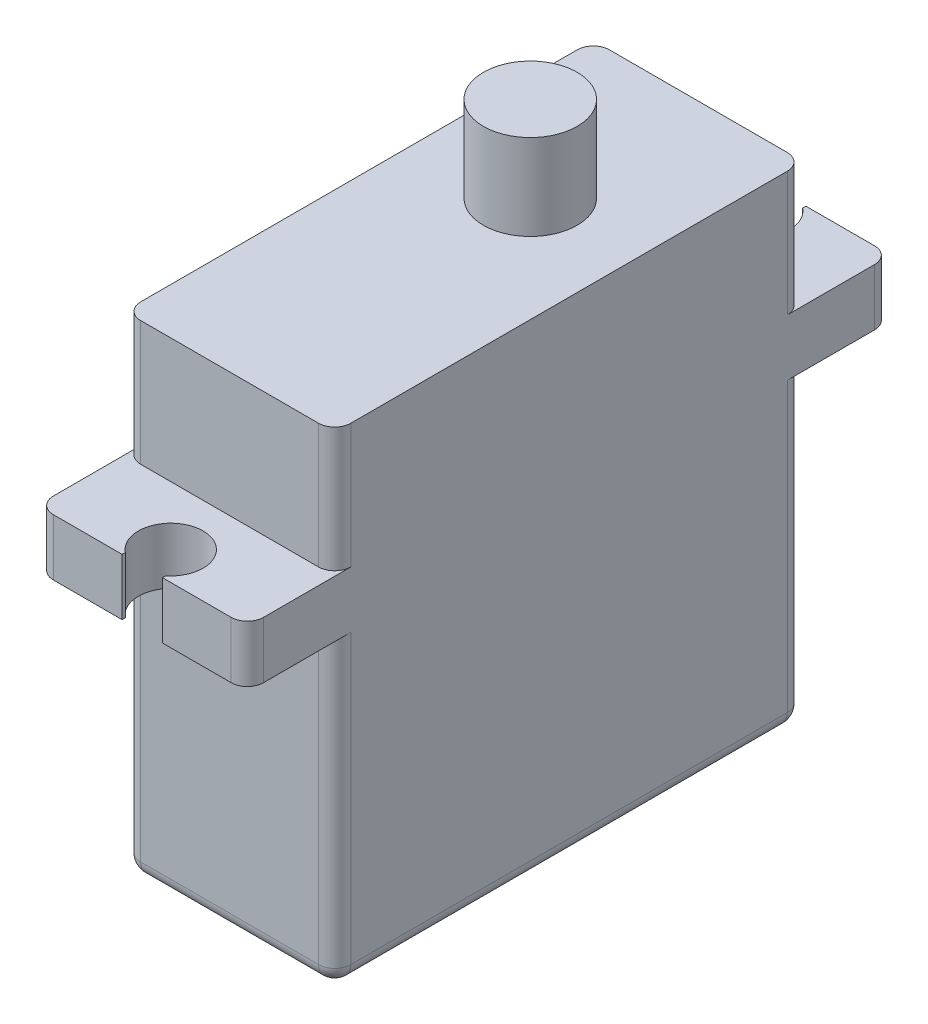
SolidWorks part; units mm, degrees
ref_plane "Front Plane" through (0, 0, 0) normal (0, 0, 1) x (1, 0, 0)
ref_plane "Top Plane" through (0, 0, 0) normal (0, 1, 0) x (1, 0, 0)
ref_plane "Right Plane" through (0, 0, 0) normal (1, 0, 0) x (0, 0, -1)
sketch "Sketch2" plane through (0, 0, 0) normal (1, 0, 0) x (0, 0, -1)
  line L1 (-14.5, 15) -> (14.5, 15)
  line L2 (-14.5, 15) -> (-14.5, -15)
  line L3 (-14.5, -15) -> (14.5, -15)
  line L4 (14.5, 15) -> (14.5, -15)
  line L5 (-14.5, 15) -> (14.5, -15) construction
  line L6 (-14.5, -15) -> (14.5, 15) construction
  line L7 (14.5, 7.3) -> (19.9, 7.3)
  line L8 (14.5, 7.3) -> (14.5, 3.8)
  line L9 (14.5, 3.8) -> (19.9, 3.8)
  line L10 (19.9, 7.3) -> (19.9, 3.8)
  line L11 (-14.5, 7.3) -> (-19.9, 7.3)
  line L12 (-14.5, 7.3) -> (-14.5, 3.8)
  line L13 (-14.5, 3.8) -> (-19.9, 3.8)
  line L14 (-19.9, 7.3) -> (-19.9, 3.8)
  line L16 (-19.9, 5.55) -> (19.9, 5.55) construction
  line L17 (1.2, 15) -> (7, 15)
  line L18 (1.2, 15) -> (1.2, 20.3)
  line L19 (1.2, 20.3) -> (7, 20.3)
  line L20 (7, 15) -> (7, 20.3)
  point P0 (0, 0)
  point P22 (0, 5.55)
  dimension "D1" = 22.3
  dimension "D2" = 29
  dimension "D3" = 35.3
  dimension "D4" = 39.8
  dimension "D5" = 30
  dimension "D6" = 3.5
  dimension "D7" = 5.8
  dimension "D8" = 7.5
extrude "Boss-Extrude1" add sketch "Sketch2" along normal blind 13 contours L4 L1 L2 L3 | L11 L14 L13 L2 | L1 L20 L19 L18 | L10 L7 L4 L9 region at (0, 0, 0) region at (0, 17.65, -4.1) region at (0, 5.55, 17.2) region at (0, 5.55, -17.2)
sketch "Sketch3" plane through (0, 15, 0) normal (0, 1, 0) x (1, 0, 0)
  line L0 (13, 7) -> (0, 7) construction
  line L1 (13, 1.2) -> (9.4, 1.2)
  line L2 (13, 1.2) -> (13, 7)
  line L3 (13, 7) -> (9.4, 7)
  line L4 (9.4, 1.2) -> (9.4, 7)
  line L5 (13, 7) -> (0, 7) construction
  line L6 (0, 1.2) -> (3.6, 1.2)
  line L7 (0, 1.2) -> (0, 7)
  line L8 (0, 7) -> (3.6, 7)
  line L9 (3.6, 1.2) -> (3.6, 7)
  line L10 (13, 19.9) -> (0, 19.9) construction
  line L11 (9.4, 7) -> (3.6, 7)
  line L12 (9.4, 1.2) -> (3.6, 1.2)
  line L15 (13, -19.9) -> (0, -19.9) construction
  line L16 (7.75, 19.9) -> (7.75, 19.7)
  line L17 (5.25, 19.9) -> (5.25, 19.7)
  line L18 (7.75, 19.9) -> (5.25, 19.9)
  line L21 (7.75, -19.9) -> (7.75, -19.7)
  line L22 (7.75, -19.9) -> (5.25, -19.9)
  line L23 (5.25, -19.9) -> (5.25, -19.7)
  circle A0 centre (6.5, 4.1) radius 2.9
  arc A1 (5.25, 19.7) -> (7.75, 19.7) centre (6.5, 18.1388) ccw
  arc A2 (7.75, -19.7) -> (5.25, -19.7) centre (6.5, -18.1388) ccw
  point P15 (3.6, 4.1)
  point P21 (6.5, 19.9)
  line M7 (13, 1.2) -> (0, 1.2)
  dimension "D1" = 4
  dimension "D2" = 2.5
  dimension "D3" = 0.2
extrude "Cut-Extrude1" cut sketch "Sketch3" along normal up to surface (5.3 mm away) contours A0 L4 M7 | A0 L4 L11 | A0 L11 L9 | A0 L9 L12 | L9 L8 L7 M7 | L4 L2 L3 M7 | A1 | A2 region at (11.2, 15, -4.1) region at (8.7522, 15, -1.8478) region at (8.7522, 15, -6.3522) region at (4.2478, 15, -1.8478) region at (4.2478, 15, -6.3522) region at (1.8, 15, -4.1) region at (6.5, 15, -18.1005) region at (6.5, 15, 18.1005) up to face at (6.5, 20.3, -4.1)
extrude "Cut-Extrude2" cut sketch "Sketch3<4>" against normal through all contours A1 | A2 region at (6.5, 15, -18.1005) region at (6.5, 15, 18.1005)
sketch "Sketch3<4>" plane through (0, 15, 0) normal (0, 1, 0) x (1, 0, 0) same geometry as "Sketch3"
fillet "Fillet1" radius 1 16 edges at (13, 5.55, 19.9) (0, 5.55, 19.9) (13, 11.15, -14.5) (6.5, -15, -14.5) (0, -15, 0) (6.5, -15, 14.5) (13, -5.6, 14.5) (13, 11.15, 14.5) (13, -15, 0) (13, -5.6, -14.5) (0, -5.6, 14.5) (0, 11.15, 14.5) (13, 5.55, -19.9) (0, 11.15, -14.5) (0, 5.55, -19.9) (0, -5.6, -14.5)
